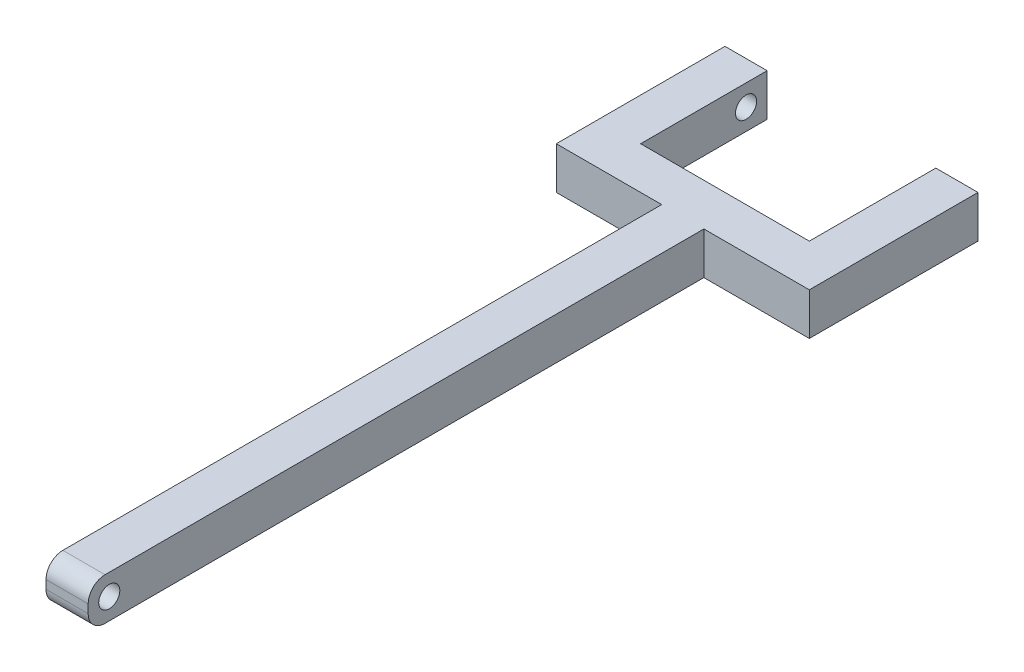
SolidWorks part; units mm, degrees
ref_plane "Front Plane" through (0, 0, 0) normal (0, 0, 1) x (1, 0, 0)
ref_plane "Top Plane" through (0, 0, 0) normal (0, 1, 0) x (1, 0, 0)
ref_plane "Right Plane" through (0, 0, 0) normal (1, 0, 0) x (0, 0, -1)
sketch "Sketch1" plane through (0, 0, 0) normal (0, 0, 1) x (1, 0, 0)
  line L1 (-6.35, -6.35) -> (6.35, -6.35)
  line L2 (-6.35, -6.35) -> (-6.35, 6.35)
  line L3 (-6.35, 6.35) -> (6.35, 6.35)
  line L4 (6.35, -6.35) -> (6.35, 6.35)
  point P4 (0, 6.35)
  point P6 (-6.35, 0)
  dimension "D1" = 12.7
  dimension "D2" = 12.7
  dimension "D3" = 0
  dimension "D4" = 0
extrude "Boss-Extrude1" add sketch "Sketch1" along normal mid plane 185.42
sketch "Sketch4" plane through (0, 0, 0) normal (1, 0, 0) x (0, 0, -1)
  line L0 (92.71, 6.35) -> (92.71, -6.35)
  line L1 (92.71, -6.35) -> (105.41, -6.35)
  line L2 (105.41, -6.35) -> (105.41, 6.35)
  line L3 (105.41, 6.35) -> (92.71, 6.35)
  dimension "D1" = 12.7
extrude "Boss-Extrude2" add sketch "Sketch4" along normal mid plane 76.2
sketch "Sketch5" plane through (0, 0, -105.41) normal (0, 0, -1) x (-1, 0, 0)
  line L0 (-38.1, 6.35) -> (38.1, 6.35) construction
  line L1 (-38.1, -6.35) -> (-25.4, -6.35)
  line L2 (-38.1, -6.35) -> (-38.1, 6.35)
  line L3 (-38.1, 6.35) -> (-25.4, 6.35)
  line L4 (-25.4, -6.35) -> (-25.4, 6.35)
  dimension "D1" = 12.7
extrude "Boss-Extrude3" add sketch "Sketch5" along normal blind 38.1
sketch "Sketch6" plane through (25.4, 0, 0) normal (-1, 0, 0) x (0, 0, 1)
  line L0 (-105.41, -6.35) -> (-105.41, 6.35) construction
  circle A0 centre (-137.16, 0) radius 3.175
  dimension "D1" = 6.35
  dimension "D2" = 31.75
extrude "Cut-Extrude1" cut sketch "Sketch6" against normal blind 6.35
mirror "Mirror1" about plane through (0, 0, 0) normal (1, 0, 0) of "Cut-Extrude1", "Boss-Extrude3"
sketch "Sketch7" plane through (-6.35, 0, 0) normal (-1, 0, 0) x (0, 0, 1)
  line L0 (92.71, 6.35) -> (92.71, -6.35) construction
  line L3 (92.71, 6.35) -> (-92.71, 6.35) construction
  circle A0 centre (86.36, 0) radius 3.175
  point P7 (84.3591, 6.35)
  point P8 (89.1347, 6.35)
  dimension "D1" = 6.35
  dimension "D2" = 6.35
  dimension "D3" = 6.35
extrude "Cut-Extrude2" cut sketch "Sketch7" against normal through all
fillet "Fillet1" radius 5.08 2 edges at (0, -6.35, 92.71) (0, 6.35, 92.71)
